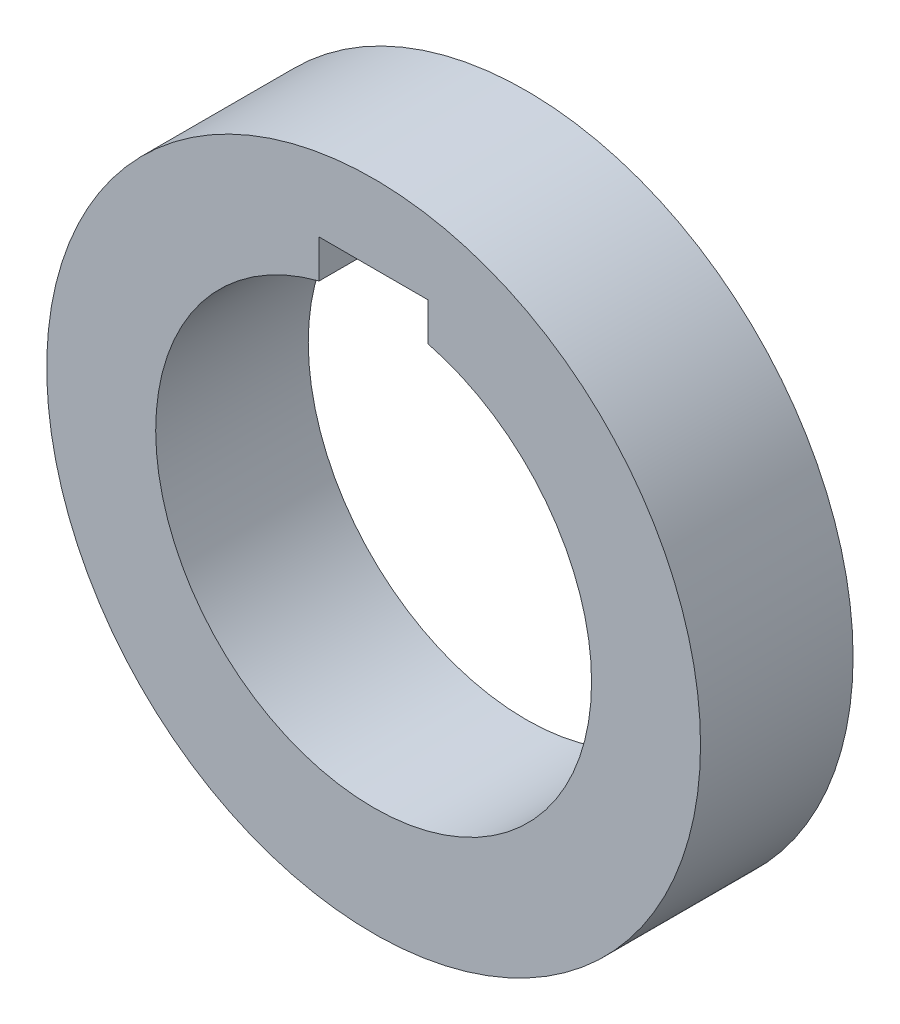
SolidWorks part; units mm, degrees
ref_plane "Front Plane" through (0, 0, 0) normal (0, 0, 1) x (1, 0, 0)
ref_plane "Top Plane" through (0, 0, 0) normal (0, 1, 0) x (1, 0, 0)
ref_plane "Right Plane" through (0, 0, 0) normal (1, 0, 0) x (0, 0, -1)
sketch "Sketch1" plane through (0, 0, 0) normal (0, 0, 1) x (1, 0, 0)
  line L0 (-2.5, 9.6825) -> (-2.5, 11.43)
  line L1 (-2.5, 11.43) -> (2.5, 11.43)
  line L2 (2.5, 11.43) -> (2.5, 9.6825)
  circle A0 centre (0, 0) radius 15
  arc A1 (-2.5, 9.6825) -> (2.5, 9.6825) centre (0, 0) ccw
  point P4 (0, 11.43)
  point P7 (0, 0)
  point P8 (0, 0)
  point P10 (-4.5083, 14.3065)
  point P11 (0, 0)
  point P13 (-0.6614, 14.9854)
  point P14 (1.115, 14.9854)
  dimension "D1" = 20
  dimension "D2" = 30
  dimension "D3" = 11.43
  dimension "D4" = 5
extrude "Boss-Extrude1" add sketch "Sketch1" along normal blind 7
